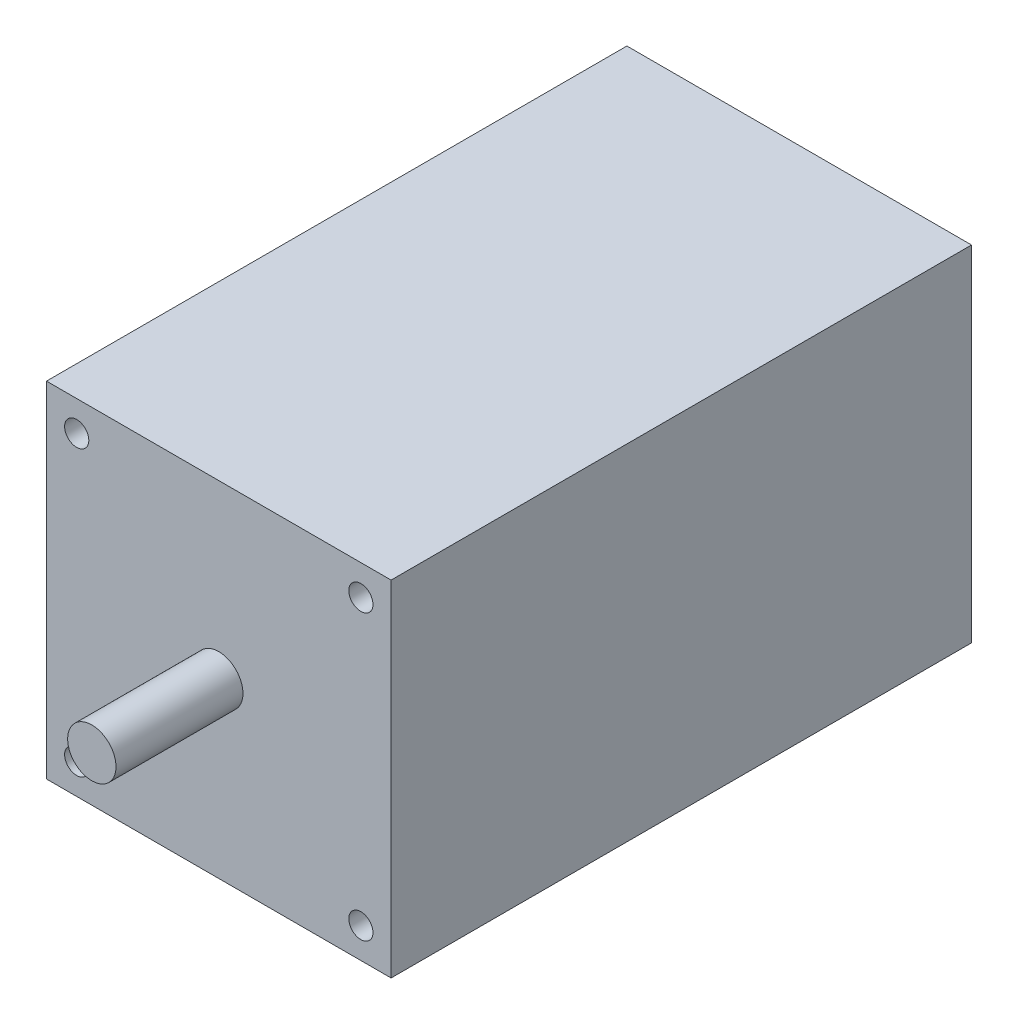
SolidWorks part; units mm, degrees
ref_plane "前基準面" through (0, 0, 0) normal (0, 0, 1) x (1, 0, 0)
ref_plane "上基準面" through (0, 0, 0) normal (0, 1, 0) x (1, 0, 0)
ref_plane "右基準面" through (0, 0, 0) normal (1, 0, 0) x (0, 0, -1)
sketch "草圖1" plane through (0, 0, 0) normal (0, 0, 1) x (1, 0, 0)
  line L1 (28.5, 28.5) -> (-28.5, 28.5)
  line L2 (28.5, 28.5) -> (28.5, -28.5)
  line L3 (28.5, -28.5) -> (-28.5, -28.5)
  line L4 (-28.5, 28.5) -> (-28.5, -28.5)
  line L5 (0, -28.5) -> (0, 28.5) construction
  line L6 (28.5, 0) -> (-28.5, 0) construction
  circle A0 centre (0, 0) radius 4 construction
  circle A1 centre (-23.5, 23.5) radius 2
  circle A2 centre (23.5, 23.5) radius 2
  circle A3 centre (23.5, -23.5) radius 2
  circle A4 centre (-23.5, -23.5) radius 2
  point P0 (0, 0)
  point P13 (0, 0)
  point P14 (0, 0)
  point P15 (-23.5, 19.007)
  point P16 (0, 0)
  dimension "D3" = 8
  dimension "D4" = 4
  dimension "D1" = 57
  dimension "D2" = 57
  dimension "D5" = 47
  dimension "D6" = 47
extrude "填料-伸長1" add sketch "草圖1" against normal blind 96
sketch "草圖2" plane through (0, 0, 0) normal (0, 0, 1) x (1, 0, 0)
  circle A0 centre (0, 0) radius 4
  dimension "D1" = 8
extrude "填料-伸長2" add sketch "草圖2" along normal blind 21
